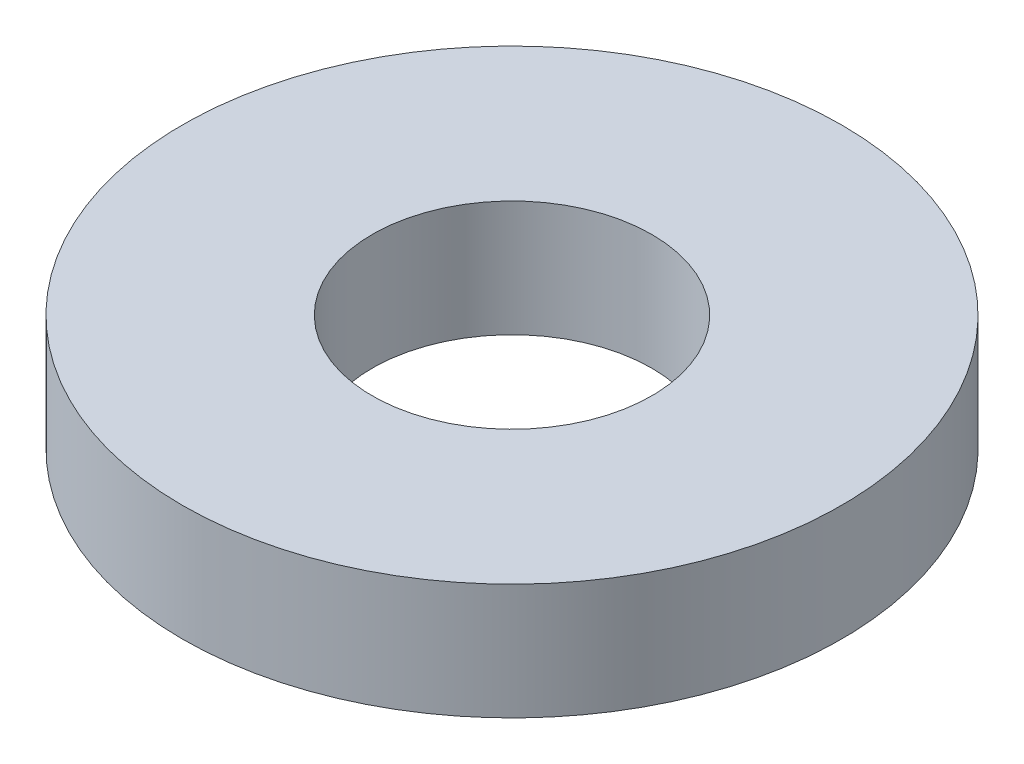
SolidWorks part; units mm, degrees
ref_plane "Front Plane" through (0, 0, 0) normal (0, 0, 1) x (1, 0, 0)
ref_plane "Top Plane" through (0, 0, 0) normal (0, 1, 0) x (1, 0, 0)
ref_plane "Right Plane" through (0, 0, 0) normal (1, 0, 0) x (0, 0, -1)
sketch "Sketch1" plane through (0, 0, 0) normal (0, 1, 0) x (1, 0, 0)
  circle A0 centre (0, 0) radius 82.5
  dimension "FLANGE_OD" = 165
extrude "Boss-Extrude1" add sketch "Sketch1" along normal blind 29
sketch "Sketch2" plane through (0, 0, 0) normal (0, 1, 0) x (1, 0, 0)
  circle A0 centre (0, 0) radius 35
  dimension "BORE_D" = 70
extrude "Cut-Extrude1" cut sketch "Sketch2" along normal through all
sketch "Sketch3" plane through (0, 29, 0) normal (0, 1, 0) x (1, 0, 0)
  circle A0 centre (0, 0) radius 27.947 construction
  circle A1 centre (-27.947, 0) radius 6.2069
  dimension "BOLT_D" = 12.4138
  dimension "BOLT_PCD" = 55.894
extrude "Cut-Extrude2" cut sketch "Sketch3" against normal blind 22.5666 rebuild error yes
pattern_circular "CirPattern1" count 5 over 360 rebuild error yes
